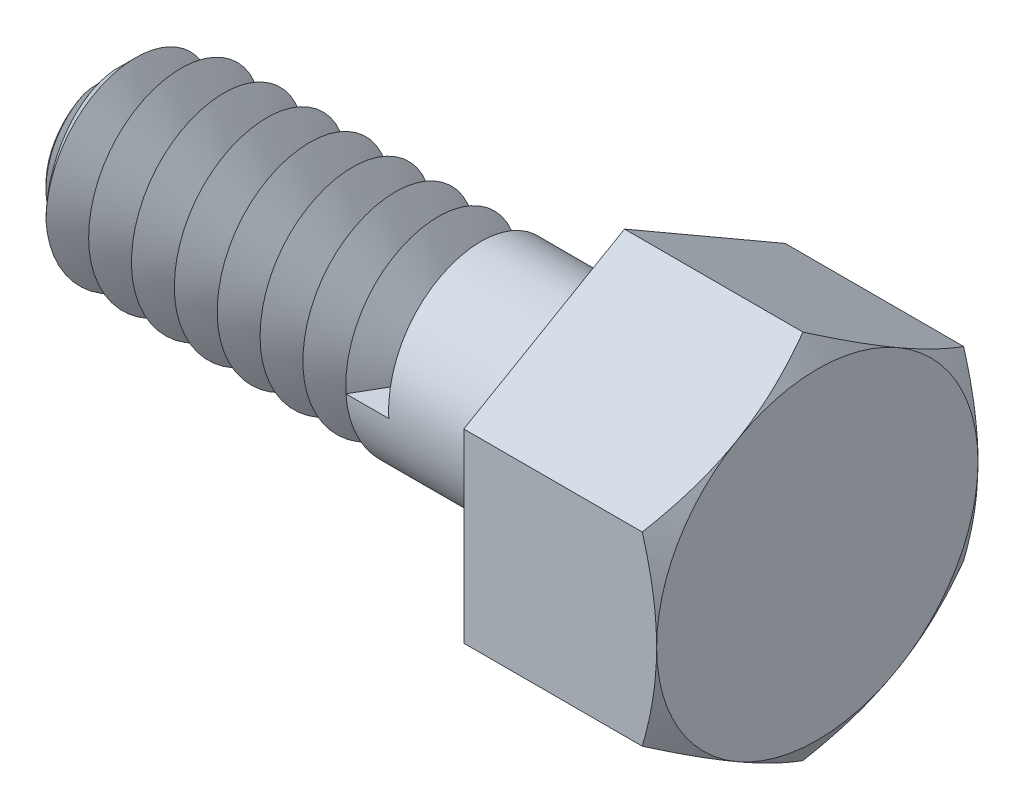
SolidWorks part; units mm, degrees
ref_plane "Front Plane" through (0, 0, 0) normal (0, 0, 1) x (1, 0, 0)
ref_plane "Top Plane" through (0, 0, 0) normal (0, 1, 0) x (1, 0, 0)
ref_plane "Right Plane" through (0, 0, 0) normal (1, 0, 0) x (0, 0, -1)
sketch "Sketch2" plane through (0, 0, 0) normal (1, 0, 0) x (0, 0, -1)
  line L1 (0, -2.8868) -> (2.5, -1.4434)
  line L2 (2.5, -1.4434) -> (2.5, 1.4434)
  line L3 (2.5, 1.4434) -> (0, 2.8868)
  line L4 (0, 2.8868) -> (-2.5, 1.4434)
  line L5 (-2.5, 1.4434) -> (-2.5, -1.4434)
  line L6 (-2.5, -1.4434) -> (0, -2.8868)
  circle A0 centre (0, 0) radius 2.5 construction
  dimension "D1" = 5
extrude "Boss-Extrude1" add sketch "Sketch2" along normal blind 3
sketch "Sketch3" plane through (3, 0, 0) normal (1, 0, 0) x (0, 0, -1)
  circle A0 centre (0, 0) radius 2.5
extrude "Cut-Extrude1" cut sketch "Sketch3" against normal blind 3 draft 60 flip side to cut
sketch "Sketch4" plane through (0, 0, 0) normal (-1, 0, 0) x (0, 0, 1)
  circle A0 centre (0, 0) radius 1.5
extrude "Boss-Extrude2" add sketch "Sketch4" along normal blind 8
chamfer "Chamfer1" distance 0.5 angle 45 1 edges at (-8, 0, 1.5)
sketch "Sketch5" plane through (-8, 0, 0) normal (-1, 0, 0) x (0, 0, 1)
  circle A0 centre (0, 0) radius 1.5
curve "Helix/Spiral1" pitch 0.6667 height 6 radius 1.5 centre (-8, 0, 0) axis (1, 0, 0) start towards (0, 0, 1)
sketch "Sketch6" plane through (0, 0, 0) normal (0, 1, 0) x (1, 0, 0)
  line L1 (-8.5, -0.9226) -> (-9, -1.7887)
  line L2 (-9, -1.7887) -> (-8, -1.7887)
  line L3 (-8, -1.7887) -> (-8.5, -0.9226)
  circle A0 centre (-8.5, -1.5) radius 0.2887 construction
sweep "Cut-Sweep1" cut profiles "Sketch6" path "Helix/Spiral1"
